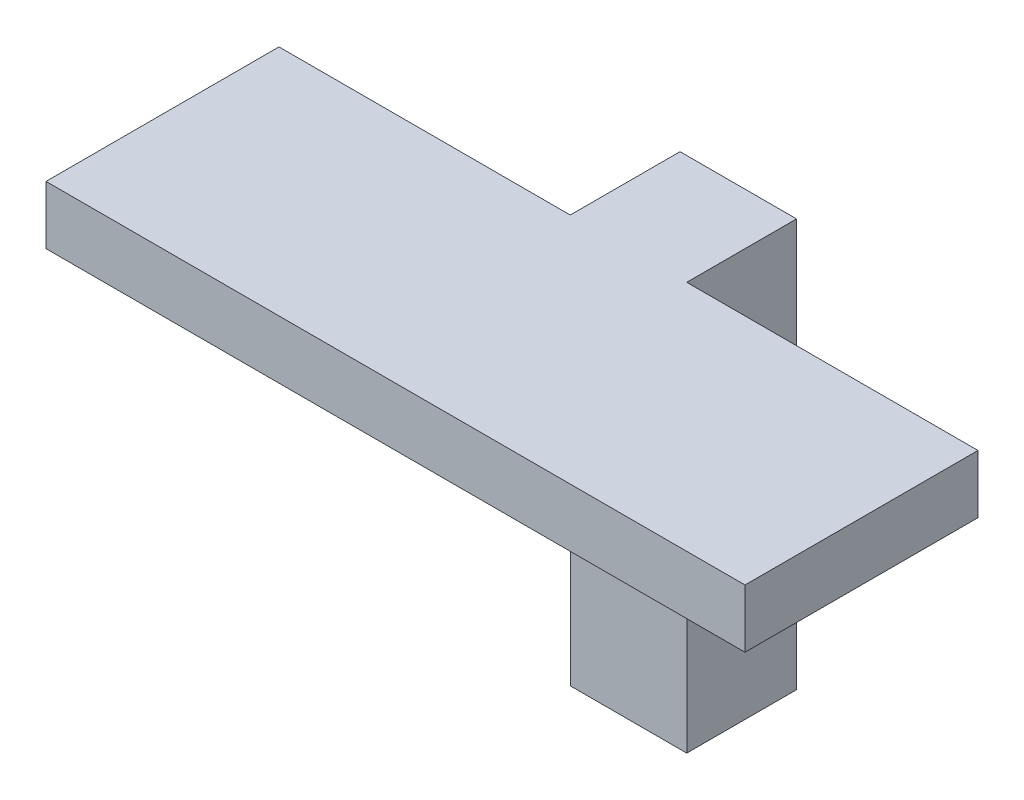
SolidWorks part; units mm, degrees
ref_plane "Front Plane" through (0, 0, 0) normal (0, 0, 1) x (1, 0, 0)
ref_plane "Top Plane" through (0, 0, 0) normal (0, 1, 0) x (1, 0, 0)
ref_plane "Right Plane" through (0, 0, 0) normal (1, 0, 0) x (0, 0, -1)
sketch "Sketch2" plane through (0, 0, 0) normal (0, 1, 0) x (1, 0, 0)
  line L0 (0, -0.2885) -> (0, 14.7115)
  line L1 (-30, 10) -> (30, 10)
  line L2 (-30, 10) -> (-30, -10)
  line L3 (-30, -10) -> (30, -10)
  line L4 (30, 10) -> (30, -10)
  line L5 (-30, 10) -> (30, -10) construction
  line L6 (-30, -10) -> (30, 10) construction
  line L8 (-5, 19.423) -> (5, 19.423)
  line L9 (-5, 19.423) -> (-5, 10)
  line L10 (-5, 10) -> (5, 10)
  line L11 (5, 19.423) -> (5, 10)
  line L12 (-5, 19.423) -> (5, 10) construction
  line L13 (-5, 10) -> (5, 19.423) construction
  point P0 (0, 0)
  dimension "D1" = 20
  dimension "D2" = 60
  dimension "D3" = 15
  dimension "D4" = 10
extrude "Boss-Extrude1" add sketch "Sketch2" along normal blind 5 contours L4 L1 L2 L3 | L11 L8 L9 L1 region at (-17.5, 0, -9.3675) region at (-4.8626, 0, -14.7115)
extrude "Boss-Extrude2" add sketch "Sketch2<3>" against normal blind 30 contours L11 L8 L9 L1 region at (-4.8626, 0, -14.7115)
sketch "Sketch2<3>" plane through (0, 0, 0) normal (0, 1, 0) x (1, 0, 0) same geometry as "Sketch2"
